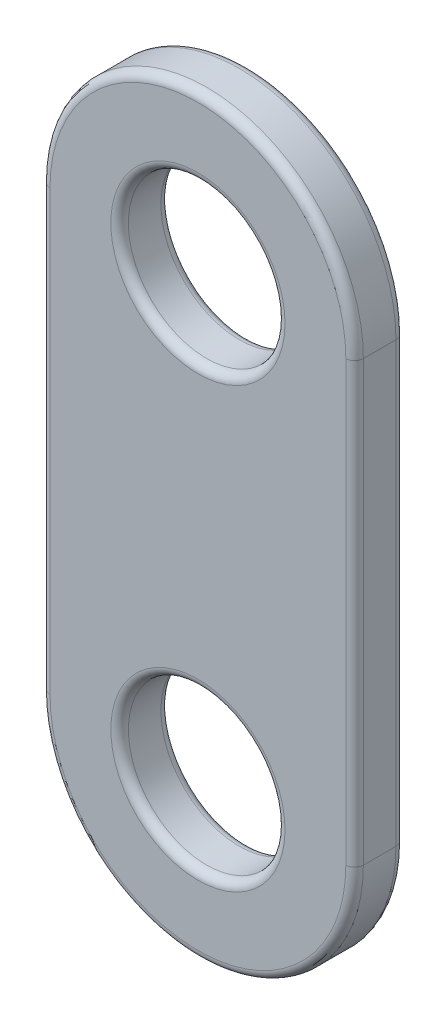
SolidWorks part; units mm, degrees
material "ABS"
ref_plane "Front Plane" through (0, 0, 0) normal (0, 0, 1) x (1, 0, 0)
ref_plane "Top Plane" through (0, 0, 0) normal (0, 1, 0) x (1, 0, 0)
ref_plane "Right Plane" through (0, 0, 0) normal (1, 0, 0) x (0, 0, -1)
sketch "Sketch1" plane through (0, 0, 0) normal (0, 0, 1) x (1, 0, 0)
  line L0 (0, 22.225) -> (0, -22.225) construction
  line L1 (-15.875, 38.1) -> (15.875, 38.1)
  line L2 (-15.875, 38.1) -> (-15.875, -38.1)
  line L3 (-15.875, -38.1) -> (15.875, -38.1)
  line L4 (15.875, 38.1) -> (15.875, -38.1)
  line L5 (-15.875, 38.1) -> (15.875, -38.1) construction
  line L6 (-15.875, -38.1) -> (15.875, 38.1) construction
  circle A0 centre (0, 22.225) radius 7.9375
  circle A2 centre (0, -22.225) radius 7.9375
  point P0 (0, 0)
  point P9 (0, 0)
  dimension "D4" = 15.875
  dimension "D1" = 31.75
  dimension "D2" = 44.45
  dimension "D3" = 76.2
extrude "Boss-Extrude1" add sketch "Sketch1" along normal blind 5.08
fillet "Fillet1" 2 edges at (15.875, 38.1, 2.54) (-15.875, 38.1, 2.54) type full round first side face at (15.875, 0, 2.54) second side face at (-15.875, 0, 2.54) middle face at (0, 38.1, 2.54)
fillet "Fillet2" 2 edges at (-15.875, -38.1, 2.54) (15.875, -38.1, 2.54) type full round first side face at (-15.875, -7.9375, 2.54) second side face at (15.875, -7.9375, 2.54) middle face at (0, -38.1, 2.54)
fillet "Fillet3" radius 0.889 12 edges at (7.9375, -22.225, 0) (7.9375, 22.225, 0) (0, 38.1, 0) (-15.875, 0, 0) (0, -38.1, 0) (15.875, 0, 0) (7.9375, -22.225, 5.08) (0, 38.1, 5.08) (15.875, 0, 5.08) (0, -38.1, 5.08) (-15.875, 0, 5.08) (7.9375, 22.225, 5.08)
